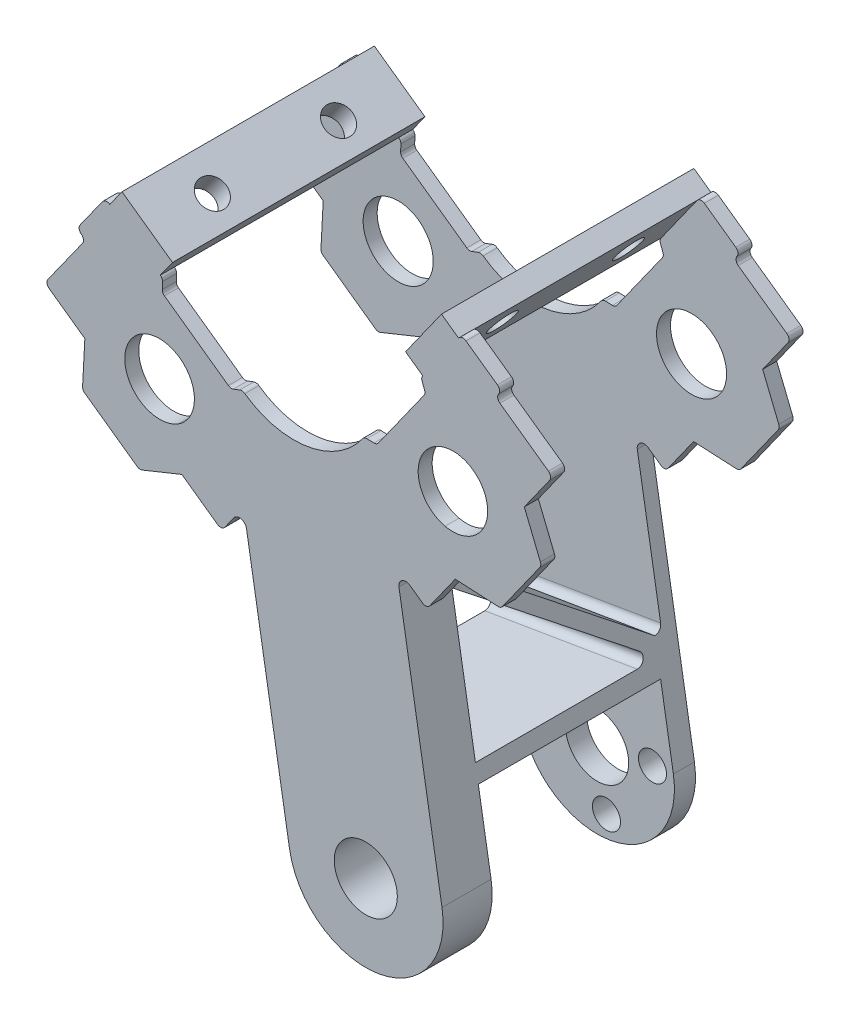
SolidWorks part; units mm, degrees
ref_plane "前视基准面" through (0, 0, 0) normal (0, 0, 1) x (1, 0, 0)
ref_plane "上视基准面" through (0, 0, 0) normal (0, 1, 0) x (1, 0, 0)
ref_plane "右视基准面" through (0, 0, 0) normal (1, 0, 0) x (0, 0, -1)
sketch "草图2" plane through (0, 0, 0) normal (0, 0, 1) x (1, 0, 0)
  circle A0 centre (0, 0) radius 73.8991
extrude "凸台-拉伸2" add sketch "草图2" along normal blind 3
sketch "草图6" plane through (0, 0, 3) normal (0, 0, 1) x (1, 0, 0)
  line L0 (-31.535, 35.3929) -> (-24.3307, 30.2552)
  line L1 (-24.0166, 29.6209) -> (-24.0481, 28.6214)
  line L2 (-23.7339, 27.9872) -> (-14.6174, 21.4858)
  line L3 (-13.9155, 21.3954) -> (-12.9807, 21.7507)
  line L6 (-15.1202, 3.7278) -> (-12.4398, 7.4864)
  line L7 (-16.1663, 3.5526) -> (-21.2549, 7.1815)
  line L8 (-21.2549, 7.1815) -> (-26.9163, 4.8902)
  line L9 (-35.1045, 10.303) -> (-27.6331, 4.9748)
  line L10 (-35.0958, 17.0522) -> (-35.4179, 10.9532)
  line L11 (-40.1844, 20.6811) -> (-35.0958, 17.0522)
  line L12 (-35.4242, 28.6476) -> (-40.3595, 21.7272)
  line L13 (-32.5811, 35.2177) -> (-35.7745, 30.7398)
  line L14 (4.9781, -29.5979) -> (0, 0) construction
  line L15 (19.2678, 43.9382) -> (23.7504, 40.7513)
  line L16 (24.1038, 38.6597) -> (31.0314, 33.7344)
  line L17 (31.2081, 32.6886) -> (27.5866, 27.5947)
  line L18 (27.5866, 27.5947) -> (29.8862, 21.9367)
  line L19 (29.8026, 21.2197) -> (24.4854, 13.7407)
  line L20 (17.7362, 13.7395) -> (23.8357, 13.4262)
  line L21 (14.1147, 8.6456) -> (17.7362, 13.7395)
  line L22 (13.0689, 8.4689) -> (9.3063, 11.1439)
  line L25 (6.1508, 24.7703) -> (5.1513, 24.8004)
  line L26 (13.2727, 34.2113) -> (6.7846, 25.0854)
  line L27 (13.0054, 35.8477) -> (13.3621, 34.9135)
  line L28 (18.222, 43.7616) -> (13.0948, 36.5498)
  line L29 (15.8511, -27.7692) -> (9.3063, 11.1439)
  line L30 (-5.895, -31.4266) -> (-12.4398, 7.4864)
  arc A0 (-5.895, -31.4266) -> (15.8511, -27.7692) centre (4.9781, -29.5979) ccw
  arc A1 (-32.5811, 35.2177) -> (-31.535, 35.3929) centre (-31.9705, 34.7823) cw
  arc A2 (-35.7745, 30.7398) -> (-35.5994, 29.6937) centre (-35.1639, 30.3043) ccw
  arc A3 (-35.4242, 28.6476) -> (-35.5994, 29.6937) centre (-36.0349, 29.0831) ccw
  arc A4 (-40.3595, 21.7272) -> (-40.1844, 20.6811) centre (-39.7489, 21.2917) ccw
  arc A5 (-24.3307, 30.2552) -> (-24.0166, 29.6209) centre (-24.7662, 29.6446) cw
  arc A6 (-24.0481, 28.6214) -> (-23.7339, 27.9872) centre (-23.2984, 28.5978) ccw
  arc A7 (-14.6174, 21.4858) -> (-13.9155, 21.3954) centre (-14.182, 22.0964) ccw
  arc A8 (-12.9807, 21.7507) -> (-12.2787, 21.6603) centre (-12.7142, 21.0497) cw
  arc A12 (-15.1202, 3.7278) -> (-16.1663, 3.5526) centre (-15.7309, 4.1632) cw
  arc A13 (-26.9163, 4.8902) -> (-27.6331, 4.9748) centre (-27.1977, 5.5855) cw
  arc A14 (-35.1045, 10.303) -> (-35.4179, 10.9532) centre (-34.669, 10.9136) cw
  arc A15 (29.8026, 21.2197) -> (29.8862, 21.9367) centre (29.1914, 21.6543) ccw
  arc A16 (23.8357, 13.4262) -> (24.4854, 13.7407) centre (23.8741, 14.1752) ccw
  arc A17 (13.0689, 8.4689) -> (14.1147, 8.6456) centre (13.5035, 9.0802) ccw
  arc A21 (5.1513, 24.8004) -> (4.5175, 24.4853) centre (5.1288, 24.0507) ccw
  arc A22 (6.7846, 25.0854) -> (6.1508, 24.7703) centre (6.1734, 25.52) cw
  arc A23 (13.3621, 34.9135) -> (13.2727, 34.2113) centre (12.6614, 34.6459) cw
  arc A24 (13.0948, 36.5498) -> (13.0054, 35.8477) centre (13.706, 36.1152) ccw
  arc A25 (31.0314, 33.7344) -> (31.2081, 32.6886) centre (30.5969, 33.1232) cw
  arc A26 (24.1038, 38.6597) -> (23.9271, 39.7055) centre (24.5384, 39.2709) cw
  arc A27 (23.7504, 40.7513) -> (23.9271, 39.7055) centre (23.3158, 40.1401) cw
  arc A28 (19.2678, 43.9382) -> (18.222, 43.7616) centre (18.8333, 43.327) ccw
  arc A29 (-12.2787, 21.6603) -> (4.5175, 24.4853) centre (-5.291, 31.4587) ccw
  point P1 (0, 0)
extrude "切除-拉伸4" cut sketch "草图6" against normal blind 10 flip side to cut
sketch "草图7" plane through (0, 0, 3) normal (0, 0, 1) x (1, 0, 0)
  line L0 (6.8068, -40.471) -> (3.6512, -21.7087) construction
  line L1 (-5.895, -31.4266) -> (15.8511, -27.7692) construction
  circle A0 centre (4.9781, -29.5979) radius 4.5
  circle A1 centre (4.9781, -29.5979) radius 8 construction
  arc A2 (-5.895, -31.4266) -> (15.8511, -27.7692) centre (4.9781, -29.5979) ccw construction
  circle A3 centre (3.6512, -21.7087) radius 2
  circle A4 centre (12.8673, -28.271) radius 2
  circle A5 centre (6.305, -37.4871) radius 2
  circle A6 centre (-2.9111, -30.9248) radius 2
  dimension "D1" = 9
  dimension "D2" = 16
  dimension "D3" = 4
  dimension "D4" = 4
  dimension "D5" = 4
  dimension "D6" = 4
extrude "切除-拉伸5" cut sketch "草图7" against normal blind 10
sketch "草图8" plane through (0, 0, 3) normal (0, 0, 1) x (1, 0, 0)
  circle A0 centre (-24.4013, 17.409) radius 5
  circle A1 centre (17.4426, 24.4153) radius 5
  dimension "D1" = 10
  dimension "D2" = 10
extrude "切除-拉伸6" cut sketch "草图8" against normal blind 10
sketch "草图9" plane through (-3.7707, -5.2873, 0) normal (-0.5806, -0.8142, 0) x (0.8142, -0.5806, 0)
  line L0 (-29.9749, 3) -> (-29.9749, -30) construction
  line L5 (-34.5632, 3) -> (-25.3866, 3) construction
  line L6 (-38.4749, -30) -> (-44.7249, -30)
  line L7 (-44.7249, 3) -> (-44.7249, -30)
  line L8 (-38.4749, 3) -> (-44.7249, 3)
  line L9 (-38.4749, 3) -> (-38.4749, -30)
  circle A2 centre (-41.4528, -24) radius 2
  circle A3 centre (-41.4528, -6) radius 2
ref_plane "基准面4" through (0, 0, 0) normal (-0.9861, -0.1659, 0) x (0, 0, 1)
mirror "镜向3" about plane through (0, 0, 0) normal (-0.9861, -0.1659, 0) of bodies 110 111
extrude "凸台-拉伸3" add sketch "草图9" against normal blind 20
sketch "草图10" plane through (-3.7707, -5.2873, 0) normal (-0.5806, -0.8142, 0) x (0.8142, -0.5806, 0)
  line L1 (-38.4749, -30) -> (-44.7249, -30)
  line L2 (-38.4749, -30) -> (-38.4749, 0)
  line L3 (-38.4749, 0) -> (-44.7249, 0)
  line L4 (-44.7249, -30) -> (-44.7249, 0)
extrude "切除-拉伸7" cut sketch "草图10" against normal blind 17 contours L2 L1 L4 L3
sketch "草图11" plane through (6.1, 8.5536, 0) normal (0.5806, 0.8142, 0) x (0.8142, -0.5806, 0)
  line L1 (-44.7249, -3) -> (-46.2249, -3)
  line L2 (-44.7249, -3) -> (-44.7249, 30)
  line L3 (-44.7249, 30) -> (-46.2249, 30)
  line L4 (-46.2249, -3) -> (-46.2249, 30)
  line L5 (-38.4749, -3) -> (-37.3763, -3)
  line L6 (-38.4749, -3) -> (-38.4749, 30)
  line L7 (-38.4749, 30) -> (-37.3763, 30)
  line L8 (-37.3763, -3) -> (-37.3763, 30)
  dimension "D1" = 1.5
  dimension "D2" = 33
  dimension "D3" = 1.0986
  dimension "D4" = 33
extrude "凸台-拉伸4" add sketch "草图11" along normal up to vertex (3 mm away)
mirror "镜向4" about plane through (0, 0, 0) normal (-0.9861, -0.1659, 0) of bodies 121
ref_plane "基准面5" through (0, 0, -30) normal (0, 0, -1) x (-1, 0, 0)
sketch "草图13" plane through (0, 0, -30) normal (0, 0, -1) x (-1, 0, 0)
  line L4 (-18.222, 43.7616) -> (-13.0948, 36.5498)
  line L5 (-13.0948, 36.5498) -> (-10.6497, 38.2881)
  line L6 (-10.6497, 38.2881) -> (-15.7769, 45.4999)
  line L8 (-18.222, 43.7616) -> (-13.0948, 36.5498)
  line L10 (-10.6497, 38.2881) -> (-15.7769, 45.4999)
  line L12 (24.3307, 30.2552) -> (31.535, 35.3929)
  line L13 (24.3307, 30.2552) -> (31.535, 35.3929)
  line L14 (29.7931, 37.8354) -> (22.5888, 32.6977)
  line L15 (31.535, 35.3929) -> (29.7931, 37.8354)
  line L18 (29.7931, 37.8354) -> (22.5888, 32.6977)
  line L20 (-13.0948, 36.5498) -> (-10.6497, 38.2881)
  line L22 (31.535, 35.3929) -> (29.7931, 37.8354)
  line L23 (22.5888, 32.6977) -> (24.3307, 30.2552)
  line L24 (22.5888, 32.6977) -> (24.3307, 30.2552)
  line L25 (-15.7769, 45.4999) -> (-18.222, 43.7616)
  line L26 (-13.0948, 36.5498) -> (-18.222, 43.7616)
  line L27 (-13.0948, 36.5498) -> (-18.222, 43.7616)
  line L28 (-15.7769, 45.4999) -> (-18.222, 43.7616)
  line L31 (31.535, 35.3929) -> (24.3307, 30.2552)
  line L33 (24.0166, 29.6209) -> (24.0481, 28.6214)
  line L34 (23.7339, 27.9872) -> (14.6174, 21.4858)
  line L35 (13.9155, 21.3954) -> (12.9807, 21.7507)
  line L36 (-5.1513, 24.8004) -> (-6.1508, 24.7703)
  line L37 (-6.7846, 25.0854) -> (-13.2727, 34.2113)
  line L38 (-13.3621, 34.9135) -> (-13.0054, 35.8477)
  line L42 (-19.2678, 43.9382) -> (-23.7504, 40.7513)
  line L43 (-24.1038, 38.6597) -> (-31.0314, 33.7344)
  line L44 (-31.2081, 32.6886) -> (-27.5866, 27.5947)
  line L45 (-27.5866, 27.5947) -> (-29.8862, 21.9367)
  line L46 (-29.8026, 21.2197) -> (-24.4854, 13.7407)
  line L47 (-23.8357, 13.4262) -> (-17.7362, 13.7395)
  line L48 (-17.7362, 13.7395) -> (-14.1147, 8.6456)
  line L49 (-13.0689, 8.4689) -> (-9.3063, 11.1439)
  line L50 (-9.3063, 11.1439) -> (-15.8511, -27.7692)
  line L51 (5.895, -31.4266) -> (12.4398, 7.4864)
  line L52 (12.4398, 7.4864) -> (15.1202, 3.7278)
  line L53 (16.1663, 3.5526) -> (21.2549, 7.1815)
  line L54 (21.2549, 7.1815) -> (26.9163, 4.8902)
  line L55 (27.6331, 4.9748) -> (35.1045, 10.303)
  line L56 (35.4179, 10.9532) -> (35.0958, 17.0522)
  line L57 (35.0958, 17.0522) -> (40.1844, 20.6811)
  line L58 (40.3595, 21.7272) -> (35.4242, 28.6476)
  line L59 (35.7745, 30.7398) -> (32.5811, 35.2177)
  line L61 (31.535, 35.3929) -> (24.3307, 30.2552)
  line L63 (24.0166, 29.6209) -> (24.0481, 28.6214)
  line L64 (23.7339, 27.9872) -> (14.6174, 21.4858)
  line L65 (13.9155, 21.3954) -> (12.9807, 21.7507)
  line L66 (-5.1513, 24.8004) -> (-6.1508, 24.7703)
  line L67 (-6.7846, 25.0854) -> (-13.2727, 34.2113)
  line L68 (-13.3621, 34.9135) -> (-13.0054, 35.8477)
  line L72 (-19.2678, 43.9382) -> (-23.7504, 40.7513)
  line L73 (-24.1038, 38.6597) -> (-31.0314, 33.7344)
  line L74 (-31.2081, 32.6886) -> (-27.5866, 27.5947)
  line L75 (-27.5866, 27.5947) -> (-29.8862, 21.9367)
  line L76 (-29.8026, 21.2197) -> (-24.4854, 13.7407)
  line L77 (-23.8357, 13.4262) -> (-17.7362, 13.7395)
  line L78 (-17.7362, 13.7395) -> (-14.1147, 8.6456)
  line L79 (-13.0689, 8.4689) -> (-9.3063, 11.1439)
  line L80 (-9.3063, 11.1439) -> (-15.8511, -27.7692)
  line L81 (5.895, -31.4266) -> (12.4398, 7.4864)
  line L82 (12.4398, 7.4864) -> (15.1202, 3.7278)
  line L83 (16.1663, 3.5526) -> (21.2549, 7.1815)
  line L84 (21.2549, 7.1815) -> (26.9163, 4.8902)
  line L85 (27.6331, 4.9748) -> (35.1045, 10.303)
  line L86 (35.4179, 10.9532) -> (35.0958, 17.0522)
  line L87 (35.0958, 17.0522) -> (40.1844, 20.6811)
  line L88 (40.3595, 21.7272) -> (35.4242, 28.6476)
  line L89 (35.7745, 30.7398) -> (32.5811, 35.2177)
  circle A1 centre (-12.8673, -28.271) radius 2
  circle A2 centre (-12.8673, -28.271) radius 2
  circle A3 centre (-3.6512, -21.7087) radius 2
  circle A4 centre (-3.6512, -21.7087) radius 2
  circle A5 centre (-4.9781, -29.5979) radius 4.5
  circle A6 centre (-4.9781, -29.5979) radius 4.5
  circle A7 centre (2.9111, -30.9248) radius 2
  circle A8 centre (2.9111, -30.9248) radius 2
  circle A9 centre (-6.305, -37.4871) radius 2
  circle A10 centre (-6.305, -37.4871) radius 2
  circle A11 centre (-17.4426, 24.4153) radius 5
  circle A12 centre (-17.4426, 24.4153) radius 5
  circle A13 centre (24.4013, 17.409) radius 5
  circle A14 centre (24.4013, 17.409) radius 5
  arc A29 (24.3307, 30.2552) -> (24.0166, 29.6209) centre (24.7662, 29.6446) ccw
  arc A30 (23.7339, 27.9872) -> (24.0481, 28.6214) centre (23.2984, 28.5978) ccw
  arc A31 (13.9155, 21.3954) -> (14.6174, 21.4858) centre (14.182, 22.0964) ccw
  arc A32 (12.9807, 21.7507) -> (12.2787, 21.6603) centre (12.7142, 21.0497) ccw
  arc A33 (-4.5175, 24.4853) -> (12.2787, 21.6603) centre (5.291, 31.4587) ccw
  arc A34 (-4.5175, 24.4853) -> (-5.1513, 24.8004) centre (-5.1288, 24.0507) ccw
  arc A35 (-6.7846, 25.0854) -> (-6.1508, 24.7703) centre (-6.1734, 25.52) ccw
  arc A36 (-13.3621, 34.9135) -> (-13.2727, 34.2113) centre (-12.6614, 34.6459) ccw
  arc A37 (-13.0054, 35.8477) -> (-13.0948, 36.5498) centre (-13.706, 36.1152) ccw
  arc A40 (-18.222, 43.7616) -> (-19.2678, 43.9382) centre (-18.8333, 43.327) ccw
  arc A41 (-23.7504, 40.7513) -> (-23.9271, 39.7055) centre (-23.3158, 40.1401) ccw
  arc A42 (-24.1038, 38.6597) -> (-23.9271, 39.7055) centre (-24.5384, 39.2709) ccw
  arc A43 (-31.0314, 33.7344) -> (-31.2081, 32.6886) centre (-30.5969, 33.1232) ccw
  arc A44 (-29.8862, 21.9367) -> (-29.8026, 21.2197) centre (-29.1914, 21.6543) ccw
  arc A45 (-24.4854, 13.7407) -> (-23.8357, 13.4262) centre (-23.8741, 14.1752) ccw
  arc A46 (-14.1147, 8.6456) -> (-13.0689, 8.4689) centre (-13.5035, 9.0802) ccw
  arc A47 (-15.8511, -27.7692) -> (5.895, -31.4266) centre (-4.9781, -29.5979) ccw
  arc A48 (15.1202, 3.7278) -> (16.1663, 3.5526) centre (15.7309, 4.1632) ccw
  arc A49 (26.9163, 4.8902) -> (27.6331, 4.9748) centre (27.1977, 5.5855) ccw
  arc A50 (35.1045, 10.303) -> (35.4179, 10.9532) centre (34.669, 10.9136) ccw
  arc A51 (40.1844, 20.6811) -> (40.3595, 21.7272) centre (39.7489, 21.2917) ccw
  arc A52 (35.5994, 29.6937) -> (35.4242, 28.6476) centre (36.0349, 29.0831) ccw
  arc A53 (35.5994, 29.6937) -> (35.7745, 30.7398) centre (35.1639, 30.3043) ccw
  arc A54 (32.5811, 35.2177) -> (31.535, 35.3929) centre (31.9705, 34.7823) ccw
  arc A57 (24.3307, 30.2552) -> (24.0166, 29.6209) centre (24.7662, 29.6446) ccw
  arc A58 (23.7339, 27.9872) -> (24.0481, 28.6214) centre (23.2984, 28.5978) ccw
  arc A59 (13.9155, 21.3954) -> (14.6174, 21.4858) centre (14.182, 22.0964) ccw
  arc A60 (12.9807, 21.7507) -> (12.2787, 21.6603) centre (12.7142, 21.0497) ccw
  arc A61 (-4.5175, 24.4853) -> (12.2787, 21.6603) centre (5.291, 31.4587) ccw
  arc A62 (-4.5175, 24.4853) -> (-5.1513, 24.8004) centre (-5.1288, 24.0507) ccw
  arc A63 (-6.7846, 25.0854) -> (-6.1508, 24.7703) centre (-6.1734, 25.52) ccw
  arc A64 (-13.3621, 34.9135) -> (-13.2727, 34.2113) centre (-12.6614, 34.6459) ccw
  arc A65 (-13.0054, 35.8477) -> (-13.0948, 36.5498) centre (-13.706, 36.1152) ccw
  arc A68 (-18.222, 43.7616) -> (-19.2678, 43.9382) centre (-18.8333, 43.327) ccw
  arc A69 (-23.7504, 40.7513) -> (-23.9271, 39.7055) centre (-23.3158, 40.1401) ccw
  arc A70 (-24.1038, 38.6597) -> (-23.9271, 39.7055) centre (-24.5384, 39.2709) ccw
  arc A71 (-31.0314, 33.7344) -> (-31.2081, 32.6886) centre (-30.5969, 33.1232) ccw
  arc A72 (-29.8862, 21.9367) -> (-29.8026, 21.2197) centre (-29.1914, 21.6543) ccw
  arc A73 (-24.4854, 13.7407) -> (-23.8357, 13.4262) centre (-23.8741, 14.1752) ccw
  arc A74 (-14.1147, 8.6456) -> (-13.0689, 8.4689) centre (-13.5035, 9.0802) ccw
  arc A75 (-15.8511, -27.7692) -> (5.895, -31.4266) centre (-4.9781, -29.5979) ccw
  arc A76 (15.1202, 3.7278) -> (16.1663, 3.5526) centre (15.7309, 4.1632) ccw
  arc A77 (26.9163, 4.8902) -> (27.6331, 4.9748) centre (27.1977, 5.5855) ccw
  arc A78 (35.1045, 10.303) -> (35.4179, 10.9532) centre (34.669, 10.9136) ccw
  arc A79 (40.1844, 20.6811) -> (40.3595, 21.7272) centre (39.7489, 21.2917) ccw
  arc A80 (35.5994, 29.6937) -> (35.4242, 28.6476) centre (36.0349, 29.0831) ccw
  arc A81 (35.5994, 29.6937) -> (35.7745, 30.7398) centre (35.1639, 30.3043) ccw
  arc A82 (32.5811, 35.2177) -> (31.535, 35.3929) centre (31.9705, 34.7823) ccw
  dimension "D1" = 0
  dimension "D2" = 0
  dimension "D3" = 0
  dimension "D4" = 0
  dimension "D5" = 0
  dimension "D6" = 0
  dimension "D7" = 0
  dimension "D8" = 0
  dimension "D9" = 0
  dimension "D10" = 0
extrude "凸台-拉伸7" add sketch "草图13" along normal blind 3 contours L10 L28 L8 L20 | L89 A82 L13 A57 L63 A58 L64 A59 L65 A60 A61 A62 L66 A63 L67 A64 L68 A65 L8 A68 L72 A69 A70 L73 A71 L74 L75 A72 L76 A73 L77 L78 A74 L79 L80 A75 L81 L82 A76 L83 L84 A77 L85 A78 L86 L87 A79 L88 A80 A81
sketch "草图15" plane through (0, 0, 0) normal (0, 0, -1) x (-1, 0, 0)
  line L0 (-9.3063, 11.1439) -> (12.4398, 7.4864)
  line L27 (31.535, 35.3929) -> (24.3307, 30.2552)
  line L28 (24.0166, 29.6209) -> (24.0481, 28.6214)
  line L29 (23.7339, 27.9872) -> (14.6174, 21.4858)
  line L30 (13.9155, 21.3954) -> (12.9807, 21.7507)
  line L31 (-5.1513, 24.8004) -> (-6.1508, 24.7703)
  line L32 (-6.7846, 25.0854) -> (-13.2727, 34.2113)
  line L33 (-13.3621, 34.9135) -> (-13.0054, 35.8477)
  line L34 (-13.0948, 36.5498) -> (-18.222, 43.7616)
  line L35 (-19.2678, 43.9382) -> (-23.7504, 40.7513)
  line L36 (-24.1038, 38.6597) -> (-31.0314, 33.7344)
  line L37 (-31.2081, 32.6886) -> (-27.5866, 27.5947)
  line L38 (-27.5866, 27.5947) -> (-29.8862, 21.9367)
  line L39 (-29.8026, 21.2197) -> (-24.4854, 13.7407)
  line L40 (-23.8357, 13.4262) -> (-17.7362, 13.7395)
  line L41 (-17.7362, 13.7395) -> (-14.1147, 8.6456)
  line L42 (-13.0689, 8.4689) -> (-9.3063, 11.1439)
  line L43 (-9.3063, 11.1439) -> (-15.8511, -27.7692)
  line L44 (5.895, -31.4266) -> (12.4398, 7.4864)
  line L45 (12.4398, 7.4864) -> (15.1202, 3.7278)
  line L46 (16.1663, 3.5526) -> (21.2549, 7.1815)
  line L47 (21.2549, 7.1815) -> (26.9163, 4.8902)
  line L48 (27.6331, 4.9748) -> (35.1045, 10.303)
  line L49 (35.4179, 10.9532) -> (35.0958, 17.0522)
  line L50 (35.0958, 17.0522) -> (40.1844, 20.6811)
  line L51 (40.3595, 21.7272) -> (35.4242, 28.6476)
  line L52 (35.7745, 30.7398) -> (32.5811, 35.2177)
  line L53 (31.535, 35.3929) -> (24.3307, 30.2552)
  line L54 (24.0166, 29.6209) -> (24.0481, 28.6214)
  line L55 (23.7339, 27.9872) -> (14.6174, 21.4858)
  line L56 (13.9155, 21.3954) -> (12.9807, 21.7507)
  line L57 (-5.1513, 24.8004) -> (-6.1508, 24.7703)
  line L58 (-6.7846, 25.0854) -> (-13.2727, 34.2113)
  line L59 (-13.3621, 34.9135) -> (-13.0054, 35.8477)
  line L60 (-13.0948, 36.5498) -> (-18.222, 43.7616)
  line L61 (-19.2678, 43.9382) -> (-23.7504, 40.7513)
  line L62 (-24.1038, 38.6597) -> (-31.0314, 33.7344)
  line L63 (-31.2081, 32.6886) -> (-27.5866, 27.5947)
  line L64 (-27.5866, 27.5947) -> (-29.8862, 21.9367)
  line L65 (-29.8026, 21.2197) -> (-24.4854, 13.7407)
  line L66 (-23.8357, 13.4262) -> (-17.7362, 13.7395)
  line L67 (-17.7362, 13.7395) -> (-14.1147, 8.6456)
  line L68 (-13.0689, 8.4689) -> (-9.3063, 11.1439)
  line L69 (-9.3063, 11.1439) -> (-15.8511, -27.7692)
  line L70 (5.895, -31.4266) -> (12.4398, 7.4864)
  line L71 (12.4398, 7.4864) -> (15.1202, 3.7278)
  line L72 (16.1663, 3.5526) -> (21.2549, 7.1815)
  line L73 (21.2549, 7.1815) -> (26.9163, 4.8902)
  line L74 (27.6331, 4.9748) -> (35.1045, 10.303)
  line L75 (35.4179, 10.9532) -> (35.0958, 17.0522)
  line L76 (35.0958, 17.0522) -> (40.1844, 20.6811)
  line L77 (40.3595, 21.7272) -> (35.4242, 28.6476)
  line L78 (35.7745, 30.7398) -> (32.5811, 35.2177)
  arc A24 (32.5811, 35.2177) -> (31.535, 35.3929) centre (31.9705, 34.7823) ccw
  arc A25 (24.3307, 30.2552) -> (24.0166, 29.6209) centre (24.7662, 29.6446) ccw
  arc A26 (23.7339, 27.9872) -> (24.0481, 28.6214) centre (23.2984, 28.5978) ccw
  arc A27 (13.9155, 21.3954) -> (14.6174, 21.4858) centre (14.182, 22.0964) ccw
  arc A28 (12.9807, 21.7507) -> (12.2787, 21.6603) centre (12.7142, 21.0497) ccw
  arc A29 (-4.5175, 24.4853) -> (12.2787, 21.6603) centre (5.291, 31.4587) ccw
  arc A30 (-4.5175, 24.4853) -> (-5.1513, 24.8004) centre (-5.1288, 24.0507) ccw
  arc A31 (-6.7846, 25.0854) -> (-6.1508, 24.7703) centre (-6.1734, 25.52) ccw
  arc A32 (-13.3621, 34.9135) -> (-13.2727, 34.2113) centre (-12.6614, 34.6459) ccw
  arc A33 (-13.0054, 35.8477) -> (-13.0948, 36.5498) centre (-13.706, 36.1152) ccw
  arc A34 (-18.222, 43.7616) -> (-19.2678, 43.9382) centre (-18.8333, 43.327) ccw
  arc A35 (-23.7504, 40.7513) -> (-23.9271, 39.7055) centre (-23.3158, 40.1401) ccw
  arc A36 (-24.1038, 38.6597) -> (-23.9271, 39.7055) centre (-24.5384, 39.2709) ccw
  arc A37 (-31.0314, 33.7344) -> (-31.2081, 32.6886) centre (-30.5969, 33.1232) ccw
  arc A38 (-29.8862, 21.9367) -> (-29.8026, 21.2197) centre (-29.1914, 21.6543) ccw
  arc A39 (-24.4854, 13.7407) -> (-23.8357, 13.4262) centre (-23.8741, 14.1752) ccw
  arc A40 (-14.1147, 8.6456) -> (-13.0689, 8.4689) centre (-13.5035, 9.0802) ccw
  arc A41 (-15.8511, -27.7692) -> (5.895, -31.4266) centre (-4.9781, -29.5979) ccw
  arc A42 (15.1202, 3.7278) -> (16.1663, 3.5526) centre (15.7309, 4.1632) ccw
  arc A43 (26.9163, 4.8902) -> (27.6331, 4.9748) centre (27.1977, 5.5855) ccw
  arc A44 (35.1045, 10.303) -> (35.4179, 10.9532) centre (34.669, 10.9136) ccw
  arc A45 (40.1844, 20.6811) -> (40.3595, 21.7272) centre (39.7489, 21.2917) ccw
  arc A46 (35.5994, 29.6937) -> (35.4242, 28.6476) centre (36.0349, 29.0831) ccw
  arc A47 (35.5994, 29.6937) -> (35.7745, 30.7398) centre (35.1639, 30.3043) ccw
  arc A48 (32.5811, 35.2177) -> (31.535, 35.3929) centre (31.9705, 34.7823) ccw
  arc A49 (24.3307, 30.2552) -> (24.0166, 29.6209) centre (24.7662, 29.6446) ccw
  arc A50 (23.7339, 27.9872) -> (24.0481, 28.6214) centre (23.2984, 28.5978) ccw
  arc A51 (13.9155, 21.3954) -> (14.6174, 21.4858) centre (14.182, 22.0964) ccw
  arc A52 (12.9807, 21.7507) -> (12.2787, 21.6603) centre (12.7142, 21.0497) ccw
  arc A53 (-4.5175, 24.4853) -> (12.2787, 21.6603) centre (5.291, 31.4587) ccw
  arc A54 (-4.5175, 24.4853) -> (-5.1513, 24.8004) centre (-5.1288, 24.0507) ccw
  arc A55 (-6.7846, 25.0854) -> (-6.1508, 24.7703) centre (-6.1734, 25.52) ccw
  arc A56 (-13.3621, 34.9135) -> (-13.2727, 34.2113) centre (-12.6614, 34.6459) ccw
  arc A57 (-13.0054, 35.8477) -> (-13.0948, 36.5498) centre (-13.706, 36.1152) ccw
  arc A58 (-18.222, 43.7616) -> (-19.2678, 43.9382) centre (-18.8333, 43.327) ccw
  arc A59 (-23.7504, 40.7513) -> (-23.9271, 39.7055) centre (-23.3158, 40.1401) ccw
  arc A60 (-24.1038, 38.6597) -> (-23.9271, 39.7055) centre (-24.5384, 39.2709) ccw
  arc A61 (-31.0314, 33.7344) -> (-31.2081, 32.6886) centre (-30.5969, 33.1232) ccw
  arc A62 (-29.8862, 21.9367) -> (-29.8026, 21.2197) centre (-29.1914, 21.6543) ccw
  arc A63 (-24.4854, 13.7407) -> (-23.8357, 13.4262) centre (-23.8741, 14.1752) ccw
  arc A64 (-14.1147, 8.6456) -> (-13.0689, 8.4689) centre (-13.5035, 9.0802) ccw
  arc A65 (-15.8511, -27.7692) -> (5.895, -31.4266) centre (-4.9781, -29.5979) ccw
  arc A66 (15.1202, 3.7278) -> (16.1663, 3.5526) centre (15.7309, 4.1632) ccw
  arc A67 (26.9163, 4.8902) -> (27.6331, 4.9748) centre (27.1977, 5.5855) ccw
  arc A68 (35.1045, 10.303) -> (35.4179, 10.9532) centre (34.669, 10.9136) ccw
  arc A69 (40.1844, 20.6811) -> (40.3595, 21.7272) centre (39.7489, 21.2917) ccw
  arc A70 (35.5994, 29.6937) -> (35.4242, 28.6476) centre (36.0349, 29.0831) ccw
  arc A71 (35.5994, 29.6937) -> (35.7745, 30.7398) centre (35.1639, 30.3043) ccw
  dimension "D1" = 0
extrude "凸台-拉伸8" add sketch "草图15" along normal blind 4 contours L69 A65 L70 L0
sketch "草图17" plane through (0, 0, -30) normal (0, 0, 1) x (1, 0, 0)
  line L0 (6.8068, -40.471) -> (3.1579, -18.7757)
  line L1 (-0.2737, 1.6271) -> (0.2737, -1.6271) construction
  line L2 (-7.7152, -20.6044) -> (14.0309, -16.9469)
  line L5 (14.0309, -16.9469) -> (13.6163, -14.4816)
  line L6 (13.6163, -14.4816) -> (-8.1298, -18.139)
  line L7 (-8.1298, -18.139) -> (-7.7152, -20.6044)
  arc A0 (-5.895, -31.4266) -> (15.8511, -27.7692) centre (4.9781, -29.5979) ccw construction
  dimension "D1" = 22
  dimension "D2" = 2.5
sketch "草图19" plane through (-10.8731, -1.8287, 0) normal (-0.9861, -0.1659, 0) x (0, 0, 1)
  line L0 (-30, -19.0394) -> (-4, -19.0394)
  line L3 (-30, -16.5394) -> (-30, -14.0394)
  line L5 (-30, -19.0394) -> (-30, -16.5394) construction
  line L7 (-4, -30.0136) -> (-4, 9.446) construction
  line L9 (-4, -19.0394) -> (-4, -16.5394)
  line L10 (-30, -19.0394) -> (-30, -16.5394)
  line L11 (-30, -16.5394) -> (-30, -19.0394) construction
  line L12 (-30, -16.5394) -> (-4, -16.5394)
  line L13 (-30, 44.6959) -> (-30, -44.6959) construction
  line L14 (-30, -14.0394) -> (0, 9.2691)
  line L15 (0, 9.2691) -> (0, 6.7691)
  line L16 (0, 10.6074) -> (0, 6.1848) construction
  line L17 (0, 6.7691) -> (-30, -16.5394)
  line L18 (-30, -16.5394) -> (-30, -14.0394)
  line M3 (-4, 9.446) -> (-4, -30.0136)
extrude "凸台-拉伸10" add sketch "草图19" along direction (0.9861, 0.1659, 0) on the side against the normal up to vertex (22.0515 mm away) contours L17 L14 L3 M3 | L12 L9 L0 L10
sketch "草图20" plane through (-10.8731, -1.8287, 0) normal (-0.9861, -0.1659, 0) x (0, 0, 1)
  line L0 (-4, 6.1613) -> (0, 9.446)
  line L1 (0, 9.446) -> (-4, 9.446)
  line L2 (-4, 9.446) -> (-4, 6.1613)
extrude "切除-拉伸8" cut sketch "草图20" against normal through all
sketch "草图21" plane through (0, 0, -4) normal (0, 0, -1) x (-1, 0, 0)
  circle A0 centre (-4.9781, -29.5979) radius 4.5 construction
  circle A1 centre (-4.9781, -29.5979) radius 4.5
extrude "切除-拉伸9" cut sketch "草图21" against normal through all contours A1
sketch "草图22" plane through (0, 0, -4) normal (0, 0, -1) x (-1, 0, 0)
  line L3 (7.7152, -20.6044) -> (-14.0309, -16.9469)
  line L4 (-14.0309, -16.9469) -> (-15.8511, -27.7692)
  line L5 (5.895, -31.4266) -> (7.7152, -20.6044)
  line L7 (-14.0309, -16.9469) -> (-15.8511, -27.7692)
  line L8 (5.895, -31.4266) -> (7.7152, -20.6044)
  line L10 (7.7152, -20.6044) -> (-14.0309, -16.9469)
  circle A0 centre (-4.9781, -29.5979) radius 4.5 construction
  arc A1 (-15.8511, -27.7692) -> (5.895, -31.4266) centre (-4.9781, -29.5979) ccw
  arc A2 (-15.8511, -27.7692) -> (5.895, -31.4266) centre (-4.9781, -29.5979) ccw
  circle A3 centre (-4.9781, -29.5979) radius 4.5
  dimension "D1" = 0
extrude "凸台-拉伸12" add sketch "草图22" against normal through all contours A3 | L10 L7 A2 L8
sketch "草图23" plane through (0, 0, 0) normal (0, 0, -1) x (-1, 0, 0)
  line L25 (-23.8357, 13.4262) -> (-17.7362, 13.7395)
  line L26 (-17.7362, 13.7395) -> (-14.1147, 8.6456)
  line L27 (-13.0689, 8.4689) -> (-9.3063, 11.1439)
  line L28 (-9.3063, 11.1439) -> (12.4398, 7.4864)
  line L29 (12.4398, 7.4864) -> (15.1202, 3.7278)
  line L30 (16.1663, 3.5526) -> (21.2549, 7.1815)
  line L31 (21.2549, 7.1815) -> (26.9163, 4.8902)
  line L32 (27.6331, 4.9748) -> (35.1045, 10.303)
  line L33 (35.4179, 10.9532) -> (35.0958, 17.0522)
  line L34 (35.0958, 17.0522) -> (40.1844, 20.6811)
  line L35 (40.3595, 21.7272) -> (35.4242, 28.6476)
  line L36 (35.7745, 30.7398) -> (32.5811, 35.2177)
  line L37 (31.535, 35.3929) -> (24.3307, 30.2552)
  line L38 (24.0166, 29.6209) -> (24.0481, 28.6214)
  line L39 (23.7339, 27.9872) -> (14.6174, 21.4858)
  line L40 (13.9155, 21.3954) -> (12.9807, 21.7507)
  line L41 (-5.1513, 24.8004) -> (-6.1508, 24.7703)
  line L42 (-6.7846, 25.0854) -> (-13.2727, 34.2113)
  line L43 (-13.3621, 34.9135) -> (-13.0054, 35.8477)
  line L44 (-13.0948, 36.5498) -> (-18.222, 43.7616)
  line L45 (-19.2678, 43.9382) -> (-23.7504, 40.7513)
  line L46 (-24.1038, 38.6597) -> (-31.0314, 33.7344)
  line L47 (-31.2081, 32.6886) -> (-27.5866, 27.5947)
  line L48 (-27.5866, 27.5947) -> (-29.8862, 21.9367)
  line L49 (-29.8026, 21.2197) -> (-24.4854, 13.7407)
  line L50 (-23.8357, 13.4262) -> (-17.7362, 13.7395)
  line L51 (-17.7362, 13.7395) -> (-14.1147, 8.6456)
  line L52 (-13.0689, 8.4689) -> (-9.3063, 11.1439)
  line L53 (-9.3063, 11.1439) -> (12.4398, 7.4864)
  line L54 (12.4398, 7.4864) -> (15.1202, 3.7278)
  line L55 (16.1663, 3.5526) -> (21.2549, 7.1815)
  line L56 (21.2549, 7.1815) -> (26.9163, 4.8902)
  line L57 (27.6331, 4.9748) -> (35.1045, 10.303)
  line L58 (35.4179, 10.9532) -> (35.0958, 17.0522)
  line L59 (35.0958, 17.0522) -> (40.1844, 20.6811)
  line L60 (40.3595, 21.7272) -> (35.4242, 28.6476)
  line L61 (35.7745, 30.7398) -> (32.5811, 35.2177)
  line L62 (31.535, 35.3929) -> (24.3307, 30.2552)
  line L63 (24.0166, 29.6209) -> (24.0481, 28.6214)
  line L64 (23.7339, 27.9872) -> (14.6174, 21.4858)
  line L65 (13.9155, 21.3954) -> (12.9807, 21.7507)
  line L66 (-5.1513, 24.8004) -> (-6.1508, 24.7703)
  line L67 (-6.7846, 25.0854) -> (-13.2727, 34.2113)
  line L68 (-13.3621, 34.9135) -> (-13.0054, 35.8477)
  line L69 (-13.0948, 36.5498) -> (-18.222, 43.7616)
  line L70 (-19.2678, 43.9382) -> (-23.7504, 40.7513)
  line L71 (-24.1038, 38.6597) -> (-31.0314, 33.7344)
  line L72 (-31.2081, 32.6886) -> (-27.5866, 27.5947)
  line L73 (-27.5866, 27.5947) -> (-29.8862, 21.9367)
  line L74 (-29.8026, 21.2197) -> (-24.4854, 13.7407)
  arc A23 (-24.4854, 13.7407) -> (-23.8357, 13.4262) centre (-23.8741, 14.1752) ccw
  arc A24 (-14.1147, 8.6456) -> (-13.0689, 8.4689) centre (-13.5035, 9.0802) ccw
  arc A25 (15.1202, 3.7278) -> (16.1663, 3.5526) centre (15.7309, 4.1632) ccw
  arc A26 (26.9163, 4.8902) -> (27.6331, 4.9748) centre (27.1977, 5.5855) ccw
  arc A27 (35.1045, 10.303) -> (35.4179, 10.9532) centre (34.669, 10.9136) ccw
  arc A28 (40.1844, 20.6811) -> (40.3595, 21.7272) centre (39.7489, 21.2917) ccw
  arc A29 (35.5994, 29.6937) -> (35.4242, 28.6476) centre (36.0349, 29.0831) ccw
  arc A30 (35.5994, 29.6937) -> (35.7745, 30.7398) centre (35.1639, 30.3043) ccw
  arc A31 (32.5811, 35.2177) -> (31.535, 35.3929) centre (31.9705, 34.7823) ccw
  arc A32 (24.3307, 30.2552) -> (24.0166, 29.6209) centre (24.7662, 29.6446) ccw
  arc A33 (23.7339, 27.9872) -> (24.0481, 28.6214) centre (23.2984, 28.5978) ccw
  arc A34 (13.9155, 21.3954) -> (14.6174, 21.4858) centre (14.182, 22.0964) ccw
  arc A35 (12.9807, 21.7507) -> (12.2787, 21.6603) centre (12.7142, 21.0497) ccw
  arc A36 (-4.5175, 24.4853) -> (12.2787, 21.6603) centre (5.291, 31.4587) ccw
  arc A37 (-4.5175, 24.4853) -> (-5.1513, 24.8004) centre (-5.1288, 24.0507) ccw
  arc A38 (-6.7846, 25.0854) -> (-6.1508, 24.7703) centre (-6.1734, 25.52) ccw
  arc A39 (-13.3621, 34.9135) -> (-13.2727, 34.2113) centre (-12.6614, 34.6459) ccw
  arc A40 (-13.0054, 35.8477) -> (-13.0948, 36.5498) centre (-13.706, 36.1152) ccw
  arc A41 (-18.222, 43.7616) -> (-19.2678, 43.9382) centre (-18.8333, 43.327) ccw
  arc A42 (-23.7504, 40.7513) -> (-23.9271, 39.7055) centre (-23.3158, 40.1401) ccw
  arc A43 (-24.1038, 38.6597) -> (-23.9271, 39.7055) centre (-24.5384, 39.2709) ccw
  arc A44 (-31.0314, 33.7344) -> (-31.2081, 32.6886) centre (-30.5969, 33.1232) ccw
  arc A45 (-29.8862, 21.9367) -> (-29.8026, 21.2197) centre (-29.1914, 21.6543) ccw
  arc A46 (-24.4854, 13.7407) -> (-23.8357, 13.4262) centre (-23.8741, 14.1752) ccw
  arc A47 (-14.1147, 8.6456) -> (-13.0689, 8.4689) centre (-13.5035, 9.0802) ccw
  arc A48 (15.1202, 3.7278) -> (16.1663, 3.5526) centre (15.7309, 4.1632) ccw
  arc A49 (26.9163, 4.8902) -> (27.6331, 4.9748) centre (27.1977, 5.5855) ccw
  arc A50 (35.1045, 10.303) -> (35.4179, 10.9532) centre (34.669, 10.9136) ccw
  arc A51 (40.1844, 20.6811) -> (40.3595, 21.7272) centre (39.7489, 21.2917) ccw
  arc A52 (35.5994, 29.6937) -> (35.4242, 28.6476) centre (36.0349, 29.0831) ccw
  arc A53 (35.5994, 29.6937) -> (35.7745, 30.7398) centre (35.1639, 30.3043) ccw
  arc A54 (32.5811, 35.2177) -> (31.535, 35.3929) centre (31.9705, 34.7823) ccw
  arc A55 (24.3307, 30.2552) -> (24.0166, 29.6209) centre (24.7662, 29.6446) ccw
  arc A56 (23.7339, 27.9872) -> (24.0481, 28.6214) centre (23.2984, 28.5978) ccw
  arc A57 (13.9155, 21.3954) -> (14.6174, 21.4858) centre (14.182, 22.0964) ccw
  arc A58 (12.9807, 21.7507) -> (12.2787, 21.6603) centre (12.7142, 21.0497) ccw
  arc A59 (-4.5175, 24.4853) -> (12.2787, 21.6603) centre (5.291, 31.4587) ccw
  arc A60 (-4.5175, 24.4853) -> (-5.1513, 24.8004) centre (-5.1288, 24.0507) ccw
  arc A61 (-6.7846, 25.0854) -> (-6.1508, 24.7703) centre (-6.1734, 25.52) ccw
  arc A62 (-13.3621, 34.9135) -> (-13.2727, 34.2113) centre (-12.6614, 34.6459) ccw
  arc A63 (-13.0054, 35.8477) -> (-13.0948, 36.5498) centre (-13.706, 36.1152) ccw
  arc A64 (-18.222, 43.7616) -> (-19.2678, 43.9382) centre (-18.8333, 43.327) ccw
  arc A65 (-23.7504, 40.7513) -> (-23.9271, 39.7055) centre (-23.3158, 40.1401) ccw
  arc A66 (-24.1038, 38.6597) -> (-23.9271, 39.7055) centre (-24.5384, 39.2709) ccw
  arc A67 (-31.0314, 33.7344) -> (-31.2081, 32.6886) centre (-30.5969, 33.1232) ccw
  arc A68 (-29.8862, 21.9367) -> (-29.8026, 21.2197) centre (-29.1914, 21.6543) ccw
  dimension "D1" = 0
extrude "切除-拉伸10" cut sketch "草图23" against normal blind 1
sketch "草图24" plane through (0, 0, -30) normal (0, 0, 1) x (1, 0, 0)
  line L27 (-8.5445, -15.6737) -> (13.2016, -12.0162)
  line L28 (13.2016, -12.0162) -> (9.3063, 11.1439)
  line L29 (9.3063, 11.1439) -> (13.0689, 8.4689)
  line L30 (14.1147, 8.6456) -> (17.7362, 13.7395)
  line L31 (17.7362, 13.7395) -> (23.8357, 13.4262)
  line L32 (24.4854, 13.7407) -> (29.8026, 21.2197)
  line L33 (29.8862, 21.9367) -> (27.5866, 27.5947)
  line L34 (27.5866, 27.5947) -> (31.2081, 32.6886)
  line L35 (31.0314, 33.7344) -> (24.1038, 38.6597)
  line L36 (23.7504, 40.7513) -> (19.2678, 43.9382)
  line L37 (18.222, 43.7616) -> (13.0948, 36.5498)
  line L38 (13.0054, 35.8477) -> (13.3621, 34.9135)
  line L39 (13.2727, 34.2113) -> (6.7846, 25.0854)
  line L40 (6.1508, 24.7703) -> (5.1513, 24.8004)
  line L41 (-12.9807, 21.7507) -> (-13.9155, 21.3954)
  line L42 (-14.6174, 21.4858) -> (-23.7339, 27.9872)
  line L43 (-24.0481, 28.6214) -> (-24.0166, 29.6209)
  line L44 (-24.3307, 30.2552) -> (-31.535, 35.3929)
  line L45 (-32.5811, 35.2177) -> (-35.7745, 30.7398)
  line L46 (-35.4242, 28.6476) -> (-40.3595, 21.7272)
  line L47 (-40.1844, 20.6811) -> (-35.0958, 17.0522)
  line L48 (-35.0958, 17.0522) -> (-35.4179, 10.9532)
  line L49 (-35.1045, 10.303) -> (-27.6331, 4.9748)
  line L50 (-26.9163, 4.8902) -> (-21.2549, 7.1815)
  line L51 (-21.2549, 7.1815) -> (-16.1663, 3.5526)
  line L52 (-15.1202, 3.7278) -> (-12.4398, 7.4864)
  line L53 (-12.4398, 7.4864) -> (-8.5445, -15.6737)
  line L54 (-8.5445, -15.6737) -> (13.2016, -12.0162)
  line L55 (13.2016, -12.0162) -> (9.3063, 11.1439)
  line L56 (9.3063, 11.1439) -> (13.0689, 8.4689)
  line L57 (14.1147, 8.6456) -> (17.7362, 13.7395)
  line L58 (17.7362, 13.7395) -> (23.8357, 13.4262)
  line L59 (24.4854, 13.7407) -> (29.8026, 21.2197)
  line L60 (29.8862, 21.9367) -> (27.5866, 27.5947)
  line L61 (27.5866, 27.5947) -> (31.2081, 32.6886)
  line L62 (31.0314, 33.7344) -> (24.1038, 38.6597)
  line L63 (23.7504, 40.7513) -> (19.2678, 43.9382)
  line L64 (18.222, 43.7616) -> (13.0948, 36.5498)
  line L65 (13.0054, 35.8477) -> (13.3621, 34.9135)
  line L66 (13.2727, 34.2113) -> (6.7846, 25.0854)
  line L67 (6.1508, 24.7703) -> (5.1513, 24.8004)
  line L68 (-12.9807, 21.7507) -> (-13.9155, 21.3954)
  line L69 (-14.6174, 21.4858) -> (-23.7339, 27.9872)
  line L70 (-24.0481, 28.6214) -> (-24.0166, 29.6209)
  line L71 (-24.3307, 30.2552) -> (-31.535, 35.3929)
  line L72 (-32.5811, 35.2177) -> (-35.7745, 30.7398)
  line L73 (-35.4242, 28.6476) -> (-40.3595, 21.7272)
  line L74 (-40.1844, 20.6811) -> (-35.0958, 17.0522)
  line L75 (-35.0958, 17.0522) -> (-35.4179, 10.9532)
  line L76 (-35.1045, 10.303) -> (-27.6331, 4.9748)
  line L77 (-26.9163, 4.8902) -> (-21.2549, 7.1815)
  line L78 (-21.2549, 7.1815) -> (-16.1663, 3.5526)
  line L79 (-15.1202, 3.7278) -> (-12.4398, 7.4864)
  line L80 (-12.4398, 7.4864) -> (-8.5445, -15.6737)
  arc A23 (13.0689, 8.4689) -> (14.1147, 8.6456) centre (13.5035, 9.0802) ccw
  arc A24 (23.8357, 13.4262) -> (24.4854, 13.7407) centre (23.8741, 14.1752) ccw
  arc A25 (29.8026, 21.2197) -> (29.8862, 21.9367) centre (29.1914, 21.6543) ccw
  arc A26 (31.2081, 32.6886) -> (31.0314, 33.7344) centre (30.5969, 33.1232) ccw
  arc A27 (23.9271, 39.7055) -> (24.1038, 38.6597) centre (24.5384, 39.2709) ccw
  arc A28 (23.9271, 39.7055) -> (23.7504, 40.7513) centre (23.3158, 40.1401) ccw
  arc A29 (19.2678, 43.9382) -> (18.222, 43.7616) centre (18.8333, 43.327) ccw
  arc A30 (13.0948, 36.5498) -> (13.0054, 35.8477) centre (13.706, 36.1152) ccw
  arc A31 (13.2727, 34.2113) -> (13.3621, 34.9135) centre (12.6614, 34.6459) ccw
  arc A32 (6.1508, 24.7703) -> (6.7846, 25.0854) centre (6.1734, 25.52) ccw
  arc A33 (5.1513, 24.8004) -> (4.5175, 24.4853) centre (5.1288, 24.0507) ccw
  arc A34 (-12.2787, 21.6603) -> (4.5175, 24.4853) centre (-5.291, 31.4587) ccw
  arc A35 (-12.2787, 21.6603) -> (-12.9807, 21.7507) centre (-12.7142, 21.0497) ccw
  arc A36 (-14.6174, 21.4858) -> (-13.9155, 21.3954) centre (-14.182, 22.0964) ccw
  arc A37 (-24.0481, 28.6214) -> (-23.7339, 27.9872) centre (-23.2984, 28.5978) ccw
  arc A38 (-24.0166, 29.6209) -> (-24.3307, 30.2552) centre (-24.7662, 29.6446) ccw
  arc A39 (-31.535, 35.3929) -> (-32.5811, 35.2177) centre (-31.9705, 34.7823) ccw
  arc A40 (-35.7745, 30.7398) -> (-35.5994, 29.6937) centre (-35.1639, 30.3043) ccw
  arc A41 (-35.4242, 28.6476) -> (-35.5994, 29.6937) centre (-36.0349, 29.0831) ccw
  arc A42 (-40.3595, 21.7272) -> (-40.1844, 20.6811) centre (-39.7489, 21.2917) ccw
  arc A43 (-35.4179, 10.9532) -> (-35.1045, 10.303) centre (-34.669, 10.9136) ccw
  arc A44 (-27.6331, 4.9748) -> (-26.9163, 4.8902) centre (-27.1977, 5.5855) ccw
  arc A45 (-16.1663, 3.5526) -> (-15.1202, 3.7278) centre (-15.7309, 4.1632) ccw
  arc A46 (13.0689, 8.4689) -> (14.1147, 8.6456) centre (13.5035, 9.0802) ccw
  arc A47 (23.8357, 13.4262) -> (24.4854, 13.7407) centre (23.8741, 14.1752) ccw
  arc A48 (29.8026, 21.2197) -> (29.8862, 21.9367) centre (29.1914, 21.6543) ccw
  arc A49 (31.2081, 32.6886) -> (31.0314, 33.7344) centre (30.5969, 33.1232) ccw
  arc A50 (23.9271, 39.7055) -> (24.1038, 38.6597) centre (24.5384, 39.2709) ccw
  arc A51 (23.9271, 39.7055) -> (23.7504, 40.7513) centre (23.3158, 40.1401) ccw
  arc A52 (19.2678, 43.9382) -> (18.222, 43.7616) centre (18.8333, 43.327) ccw
  arc A53 (13.0948, 36.5498) -> (13.0054, 35.8477) centre (13.706, 36.1152) ccw
  arc A54 (13.2727, 34.2113) -> (13.3621, 34.9135) centre (12.6614, 34.6459) ccw
  arc A55 (6.1508, 24.7703) -> (6.7846, 25.0854) centre (6.1734, 25.52) ccw
  arc A56 (5.1513, 24.8004) -> (4.5175, 24.4853) centre (5.1288, 24.0507) ccw
  arc A57 (-12.2787, 21.6603) -> (4.5175, 24.4853) centre (-5.291, 31.4587) ccw
  arc A58 (-12.2787, 21.6603) -> (-12.9807, 21.7507) centre (-12.7142, 21.0497) ccw
  arc A59 (-14.6174, 21.4858) -> (-13.9155, 21.3954) centre (-14.182, 22.0964) ccw
  arc A60 (-24.0481, 28.6214) -> (-23.7339, 27.9872) centre (-23.2984, 28.5978) ccw
  arc A61 (-24.0166, 29.6209) -> (-24.3307, 30.2552) centre (-24.7662, 29.6446) ccw
  arc A62 (-31.535, 35.3929) -> (-32.5811, 35.2177) centre (-31.9705, 34.7823) ccw
  arc A63 (-35.7745, 30.7398) -> (-35.5994, 29.6937) centre (-35.1639, 30.3043) ccw
  arc A64 (-35.4242, 28.6476) -> (-35.5994, 29.6937) centre (-36.0349, 29.0831) ccw
  arc A65 (-40.3595, 21.7272) -> (-40.1844, 20.6811) centre (-39.7489, 21.2917) ccw
  arc A66 (-35.4179, 10.9532) -> (-35.1045, 10.303) centre (-34.669, 10.9136) ccw
  arc A67 (-27.6331, 4.9748) -> (-26.9163, 4.8902) centre (-27.1977, 5.5855) ccw
  arc A68 (-16.1663, 3.5526) -> (-15.1202, 3.7278) centre (-15.7309, 4.1632) ccw
  dimension "D1" = 0
extrude "切除-拉伸11" cut sketch "草图24" against normal blind 1
fillet "圆角1" radius 1 3 edges at (-8.5445, -15.6737, -30.5) (2.3286, -13.8449, -31) (13.2016, -12.0162, -30.5)
fillet "圆角2" radius 1 1 edges at (2.7432, -16.3103, -30)
fillet "圆角3" radius 1 1 edges at (9.3063, 11.1439, -32)
fillet "圆角4" radius 1 1 edges at (-12.4398, 7.4864, -32)
fillet "圆角5" radius 1 1 edges at (-12.4398, 7.4864, 2)
fillet "圆角11" radius 2.75 4 edges at (9.3063, 11.1439, 0.5) (-12.4398, 7.4864, 0.5) (-1.5667, 9.3152, 0) (9.5787, 9.5243, -2)
fillet "圆角12" radius 1 1 edges at (9.3063, 11.1439, 2)
